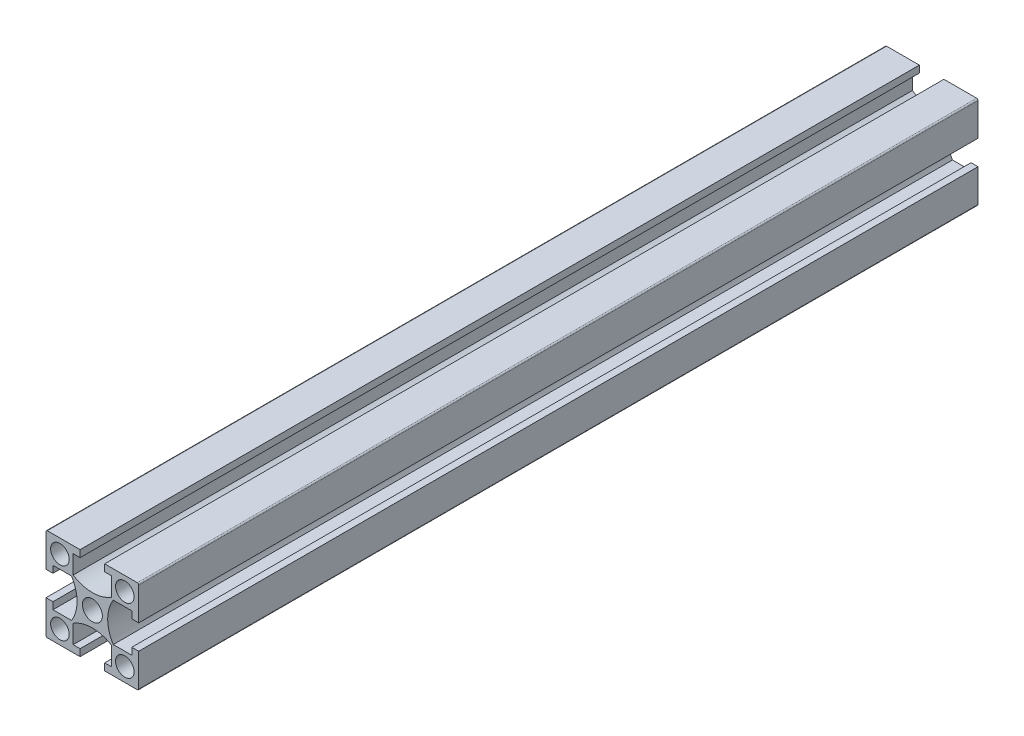
SolidWorks part; units mm, degrees
ref_plane "정면" through (0, 0, 0) normal (0, 0, 1) x (1, 0, 0)
ref_plane "윗면" through (0, 0, 0) normal (0, 1, 0) x (1, 0, 0)
ref_plane "우측면" through (0, 0, 0) normal (1, 0, 0) x (0, 0, -1)
sketch "스케치1" plane through (0, 0, 0) normal (0, 0, 1) x (1, 0, 0)
  line L0 (0, 32.0265) -> (0, -31.6588) construction
  line L1 (-10, 10) -> (-10, -10)
  line L2 (-10, 10) -> (10, 10)
  line L3 (-10, 2.65) -> (-8.5, 2.65)
  line L4 (13.6618, 0) -> (-11.6993, 0) construction
  line L5 (-8.5, 2.65) -> (-8.5, 4.15)
  line L6 (-8.5, 4.15) -> (-4.5032, 4.15)
  line L7 (-10, -2.65) -> (-8.5, -2.65)
  line L8 (-8.5, -2.65) -> (-8.5, -4.15)
  line L9 (-8.5, -4.15) -> (-4.5032, -4.15)
  line L10 (-10, -10) -> (10, -10)
  line L11 (10, 10) -> (10, -10)
  circle A0 centre (-7, 7) radius 2
  circle A1 centre (-7, -7) radius 2
  arc A2 (-4.5032, 4.15) -> (-4.5032, -4.15) centre (-11.0587, 0) cw
  circle A3 centre (0, 0) radius 2.15
  circle A4 centre (7, 7) radius 2
  circle A5 centre (7, -7) radius 2
  point P21 (-10, 0)
  point P23 (-3.3, 0)
  point P31 (0, -10)
  point P32 (0, 10)
  dimension "D3" = 4
  dimension "D9" = 6.7
  dimension "D10" = 4.3
  dimension "D11" = 7.7587
  dimension "D1" = 20
  dimension "D2" = 20
  dimension "D4" = 14
  dimension "D5" = 14
  dimension "D6" = 5.3
  dimension "D7" = 8.3
  dimension "D8" = 1.5
extrude "보스-돌출1" add sketch "스케치1" along normal blind 181 contours A0 | A4 | A3 | A5 | A1 | A2 L6 L5 L3 L1 L7 L8 L9 | L2 L11 L10 L1 region at (-6.6069, 0, 0) region at (-7, 7, 0) region at (-7, -7, 0) region at (0, 0, 0) region at (7, 7, 0) region at (7, -7, 0)
extrude "컷-돌출1" cut sketch "스케치1<3>" along normal up to next contours A2 L6 L5 L3 L1 L7 L8 L9 region at (-6.6069, 0, 0)
sketch "스케치1<3>" plane through (0, 0, 0) normal (0, 0, 1) x (1, 0, 0) same geometry as "스케치1"
pattern_circular "원형 패턴1" count 4 over 360 about axis through (0, 0, 181) along (0, 0, -1) of "컷-돌출1" reverse direction yes
fillet "필렛1" radius 0.3 4 edges at (10, -10, 90.5) (-10, -10, 90.5) (-10, 10, 90.5) (10, 10, 90.5)
sketch "스케치2" plane through (-10, 0, 0) normal (-1, 0, 0) x (0, 0, 1)
  circle A1 centre (11, 0) radius 2.5
extrude "컷-돌출2" cut sketch "스케치2" against normal through all
